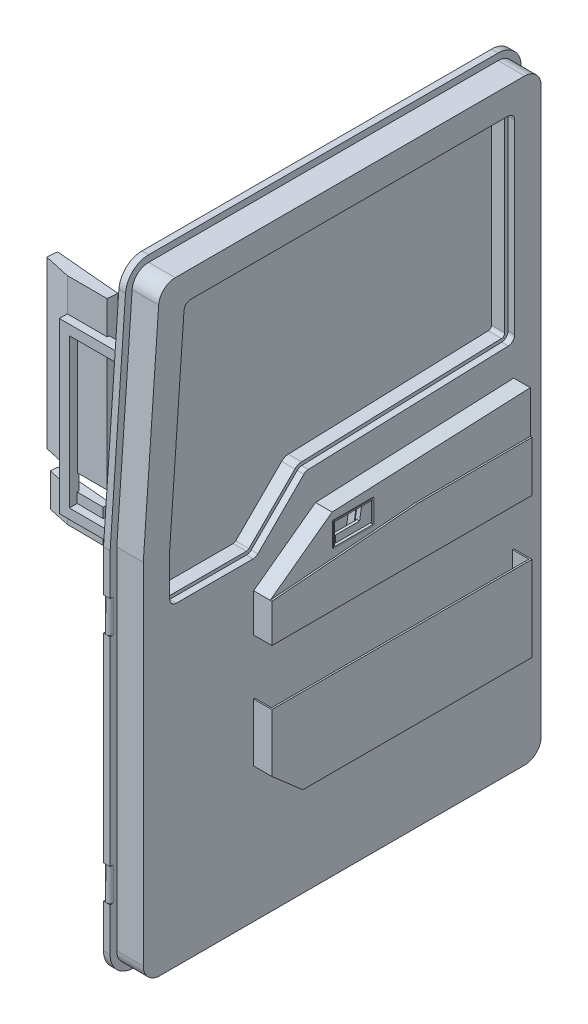
SolidWorks part; units mm, degrees
ref_plane "Front Plane" through (0, 0, 0) normal (0, 0, 1) x (1, 0, 0)
ref_plane "Top Plane" through (0, 0, 0) normal (0, 1, 0) x (1, 0, 0)
ref_plane "Right Plane" through (0, 0, 0) normal (1, 0, 0) x (0, 0, -1)
ref_plane "Plane1" through (950, 0, 0) normal (1, 0, 0) x (0, 0, -1)
sketch "Sketch1" plane through (950, 0, 0) normal (1, 0, 0) x (0, 0, -1)
  line L0 (-750, -200) -> (-750, 1110) construction
  line L1 (-550, 0) -> (550, 0)
  line L2 (-600, 50) -> (-600, 1104.6439)
  line L3 (-503.7259, 1800) -> (550, 1800)
  line L4 (600, 50) -> (600, 1750)
  line L5 (-750, 1110) -> (-699.9479, 1809.9761) construction
  line L6 (-699.9479, 1809.9761) -> (-739.9479, 1809.9761) construction
  line L7 (-739.9479, 1809.9761) -> (-739.9479, 1909.9761) construction
  line L8 (-750, -200) -> (600, -200) construction
  line L9 (600, -200) -> (600, 0) construction
  line L10 (-600, 1104.6439) -> (-553.5985, 1753.5662)
  line L11 (-503.7259, 1820) -> (550, 1820)
  line L12 (620, 50) -> (620, 1750)
  line L13 (-550, -20) -> (550, -20)
  line L14 (-620, 50) -> (-620, 1105.3581)
  line L15 (-620, 1105.3581) -> (-573.5476, 1754.9926)
  arc A0 (-553.5985, 1753.5662) -> (-503.7259, 1800) centre (-503.7259, 1750) cw
  arc A1 (550, 1800) -> (600, 1750) centre (550, 1750) cw
  arc A2 (550, 0) -> (600, 50) centre (550, 50) ccw
  arc A3 (-550, 0) -> (-600, 50) centre (-550, 50) cw
  arc A4 (550, 1820) -> (620, 1750) centre (550, 1750) cw
  arc A5 (550, -20) -> (620, 50) centre (550, 50) ccw
  arc A6 (-550, -20) -> (-620, 50) centre (-550, 50) cw
  arc A7 (-573.5476, 1754.9926) -> (-503.7259, 1820) centre (-503.7259, 1750) cw
  point P16 (600, 1800)
  point P22 (-600, 0)
  dimension "D11" = 50
  dimension "D1" = 1200
  dimension "D2" = 1800
  dimension "D3" = 200
  dimension "D4" = 100
  dimension "D5" = 40
  dimension "D6" = 2110
  dimension "D7" = 150
  dimension "D8" = 1310
  dimension "D9" = 175.91
  dimension "D10" = 150
  dimension "D12" = 20
extrude "Boss-Extrude1" add sketch "Sketch1" against normal blind 20
extrude "Boss-Extrude2" add sketch "Sketch1<2>" against normal blind 100 contours A3 L1 A2 L4 A1 L3 A0 L10 L2 region at (950, 894.6381, -4.6785)
sketch "Sketch1<2>" plane through (950, 0, 0) normal (1, 0, 0) x (0, 0, -1) same geometry as "Sketch1"
sketch "Sketch2" plane through (950, 0, 0) normal (1, 0, 0) x (0, 0, -1)
  line L9 (-520.2547, 1098.2257) -> (-520.2547, 968.2257)
  line L10 (-500.2547, 948.2257) -> (-268.6753, 948.2257)
  line L11 (-254.5499, 954.0669) -> (-115.6202, 1092.6683)
  line L12 (520, 50) -> (520, 1720)
  line L13 (520, 1720) -> (-475.7944, 1720)
  line L14 (-475.7944, 1720) -> (-520.2547, 1098.2257)
  line L15 (520, 1139.3207) -> (520, 1700)
  line L16 (500, 1720) -> (-457.1735, 1720)
  line L17 (-477.1225, 1701.4265) -> (-520.2547, 1098.2257)
  line L18 (-102.1855, 1098.4975) -> (500.6908, 1119.3327)
  line L19 (500, 1710) -> (-457.1735, 1710)
  line L20 (-467.148, 1700.7132) -> (-510.2547, 1097.8687)
  line L21 (-510.2547, 1097.8687) -> (-510.2547, 968.2257)
  line L22 (-500.2547, 958.2257) -> (-268.6753, 958.2257)
  line L23 (-261.6126, 961.1463) -> (-122.6829, 1099.7477)
  line L24 (-102.5309, 1108.4915) -> (500.3454, 1129.3267)
  line L25 (510, 1139.3207) -> (510, 1700)
  arc A6 (520, 1700) -> (500, 1720) centre (500, 1700) ccw
  arc A7 (500.6908, 1119.3327) -> (520, 1139.3207) centre (500, 1139.3207) ccw
  arc A8 (-115.6202, 1092.6683) -> (-102.1855, 1098.4975) centre (-101.4948, 1078.5094) cw
  arc A9 (-268.6753, 948.2257) -> (-254.5499, 954.0669) centre (-268.6753, 968.2257) ccw
  arc A10 (-457.1735, 1720) -> (-477.1225, 1701.4265) centre (-457.1735, 1700) ccw
  arc A11 (-520.2547, 968.2257) -> (-500.2547, 948.2257) centre (-500.2547, 968.2257) ccw
  arc A12 (-457.1735, 1710) -> (-467.148, 1700.7132) centre (-457.1735, 1700) ccw
  arc A13 (-510.2547, 968.2257) -> (-500.2547, 958.2257) centre (-500.2547, 968.2257) ccw
  arc A14 (-268.6753, 958.2257) -> (-261.6126, 961.1463) centre (-268.6753, 968.2257) ccw
  arc A15 (-122.6829, 1099.7477) -> (-102.5309, 1108.4915) centre (-101.4948, 1078.5094) cw
  arc A16 (500.3454, 1129.3267) -> (510, 1139.3207) centre (500, 1139.3207) ccw
  arc A17 (510, 1700) -> (500, 1710) centre (500, 1700) ccw
  point P13 (520, 1120)
  point P16 (-110.0496, 1098.2257)
  point P19 (-260.4048, 948.2257)
  point P25 (-520.2547, 948.2257)
  dimension "D6" = 20
  dimension "D2" = 600
  dimension "D3" = 621.7743
  dimension "D4" = 150
  dimension "D5" = 150
  dimension "D1" = 100
  dimension "D7" = 10
extrude "Cut-Extrude1" cut sketch "Sketch2" against normal blind 20
extrude "Cut-Extrude2" cut sketch "Sketch2<2>" against normal blind 30 contours L25 A17 L19 A12 L20 L21 A13 L22 A14 L23 A15 L24 A16 region at (950, 1382.3885, 18.9303)
sketch "Sketch2<2>" plane through (950, 0, 0) normal (1, 0, 0) x (0, 0, -1) same geometry as "Sketch2"
sketch "Sketch3" plane through (850, 0, 0) normal (-1, 0, 0) x (0, 0, 1)
  line L0 (-520, 1700) -> (-520, 1139.3207)
  line L1 (-500, 1710) -> (457.1735, 1710)
  line L2 (-500.6908, 1119.3327) -> (102.1855, 1098.4975)
  line L3 (115.6202, 1092.6683) -> (254.5499, 954.0669)
  line L4 (268.6753, 948.2257) -> (500.2547, 948.2257)
  line L5 (520.2547, 968.2257) -> (520.2547, 1098.2257)
  line L6 (520.2547, 1098.2257) -> (477.1225, 1701.4265)
  line L7 (-500, 1720) -> (457.1735, 1720)
  line L8 (510.2547, 1097.8687) -> (467.148, 1700.7132)
  line L9 (510.2547, 968.2257) -> (510.2547, 1097.8687)
  line L10 (268.6753, 958.2257) -> (500.2547, 958.2257)
  line L11 (122.6829, 1099.7477) -> (261.6126, 961.1463)
  line L12 (-500.3454, 1129.3267) -> (102.5309, 1108.4915)
  line L13 (-510, 1700) -> (-510, 1139.3207)
  arc A0 (-520, 1139.3207) -> (-500.6908, 1119.3327) centre (-500, 1139.3207) ccw
  arc A1 (102.1855, 1098.4975) -> (115.6202, 1092.6683) centre (101.4948, 1078.5094) cw
  arc A2 (254.5499, 954.0669) -> (268.6753, 948.2257) centre (268.6753, 968.2257) ccw
  arc A5 (254.5499, 954.0669) -> (268.6753, 948.2257) centre (268.6753, 968.2257) ccw construction
  arc A6 (500.2547, 948.2257) -> (520.2547, 968.2257) centre (500.2547, 968.2257) ccw
  arc A7 (457.1735, 1720) -> (477.1225, 1701.4265) centre (457.1735, 1700) cw
  arc A8 (-520, 1700) -> (-500, 1720) centre (-500, 1700) cw
  arc A9 (-510, 1700) -> (-500, 1710) centre (-500, 1700) cw
  arc A10 (457.1735, 1710) -> (467.148, 1700.7132) centre (457.1735, 1700) cw
  arc A11 (500.2547, 958.2257) -> (510.2547, 968.2257) centre (500.2547, 968.2257) ccw
  arc A12 (261.6126, 961.1463) -> (268.6753, 958.2257) centre (268.6753, 968.2257) ccw
  arc A13 (102.5309, 1108.4915) -> (122.6829, 1099.7477) centre (101.4948, 1078.5094) cw
  arc A14 (-510, 1139.3207) -> (-500.3454, 1129.3267) centre (-500, 1139.3207) ccw
  dimension "D1" = 10
extrude "Cut-Extrude3" cut sketch "Sketch3" against normal blind 20
extrude "Cut-Extrude4" cut sketch "Sketch3<2>" against normal blind 60 contours L13 A14 L12 A13 L11 A12 L10 A11 L9 L8 A10 L1 A9 region at (850, 1382.3885, 18.9303)
sketch "Sketch3<2>" plane through (850, 0, 0) normal (-1, 0, 0) x (0, 0, 1) same geometry as "Sketch3"
ref_plane "Plane2" through (0, 180, 0) normal (0, -1, 0) x (1, 0, 0)
sketch "Sketch4" plane through (0, 180, 0) normal (0, -1, 0) x (1, 0, 0)
  line L0 (930, 573.5476) -> (930, 620) construction
  line L2 (930, 620) -> (950, 620) construction
  line L3 (930, 610) -> (930, 624.5561)
  line L4 (930, 624.5561) -> (950, 624.5561)
  line L5 (950, 624.5561) -> (950, 610)
  circle A0 centre (940, 610) radius 10
  dimension "D1" = 20
extrude "Cut-Extrude5" cut sketch "Sketch4" against normal blind 100 contours A0 L5 L4 L3 region at (940, 180, 620.8334)
pattern_linear "LPattern1" count 2 spacing 700 along (0, 1, 0) of "Cut-Extrude5"
sketch "Sketch5" plane through (950, 0, 0) normal (1, 0, 0) x (0, 0, -1)
  line L0 (620, 50) -> (620, 1750) construction
  line L1 (460, 130) -> (300, 130)
  line L2 (470, 140) -> (470, 240)
  line L3 (460, 250) -> (300, 250)
  line L4 (290, 140) -> (290, 240)
  line L5 (-550, -20) -> (550, -20) construction
  line L6 (460, 253) -> (300, 253)
  line L7 (287, 140) -> (287, 240)
  line L8 (460, 127) -> (300, 127)
  line L9 (473, 140) -> (473, 240)
  arc A0 (470, 240) -> (460, 250) centre (460, 240) ccw
  arc A1 (460, 130) -> (470, 140) centre (460, 140) ccw
  arc A2 (300, 130) -> (290, 140) centre (300, 140) cw
  arc A3 (300, 250) -> (290, 240) centre (300, 240) ccw
  arc A4 (300, 253) -> (287, 240) centre (300, 240) ccw
  arc A5 (300, 127) -> (287, 140) centre (300, 140) cw
  arc A6 (460, 127) -> (473, 140) centre (460, 140) ccw
  arc A7 (473, 240) -> (460, 253) centre (460, 240) ccw
  point P10 (470, 250)
  point P13 (470, 130)
  point P16 (290, 130)
  dimension "D5" = 10
  dimension "D1" = 120
  dimension "D2" = 150
  dimension "D3" = 150
  dimension "D4" = 180
  dimension "D6" = 3
extrude "Cut-Extrude6" cut sketch "Sketch5" against normal blind 10 contours L3 A3 L4 A2 L1 A1 L2 A0 region at (950, 190, -380)
extrude "Boss-Extrude3" add sketch "Sketch5<3>" along normal blind 3
sketch "Sketch5<3>" plane through (950, 0, 0) normal (1, 0, 0) x (0, 0, -1) same geometry as "Sketch5"
sketch "Sketch6" plane through (940, 0, 0) normal (1, 0, 0) x (0, 0, -1)
  line L0 (300, 130) -> (460, 130) construction
  line L1 (305, 240) -> (445, 240)
  line L2 (300, 235) -> (300, 145)
  line L3 (305, 140) -> (445, 140)
  line L4 (450, 235) -> (450, 145)
  line L5 (290, 240) -> (290, 140) construction
  arc A0 (300, 145) -> (305, 140) centre (305, 145) ccw
  arc A1 (445, 140) -> (450, 145) centre (445, 145) ccw
  arc A2 (445, 240) -> (450, 235) centre (445, 235) cw
  arc A3 (305, 240) -> (300, 235) centre (305, 235) ccw
  point P10 (300, 140)
  point P15 (450, 240)
  point P18 (300, 240)
  dimension "D5" = 5
  dimension "D1" = 150
  dimension "D2" = 100
  dimension "D3" = 10
  dimension "D4" = 10
extrude "Boss-Extrude4" add sketch "Sketch6" along normal blind 10
sketch "Sketch10" plane through (950, 0, 0) normal (1, 0, 0) x (0, 0, -1)
  line L0 (324.7973, 190) -> (300, 190) construction
  line L1 (325.7973, 195) -> (323.7973, 195)
  line L2 (325.7973, 195) -> (325.7973, 185)
  line L3 (325.7973, 185) -> (323.7973, 185)
  line L4 (323.7973, 195) -> (323.7973, 185)
  line L5 (325.7973, 195) -> (323.7973, 185) construction
  line L6 (325.7973, 185) -> (323.7973, 195) construction
  line L7 (300, 235) -> (300, 145) construction
  circle A0 centre (324.7973, 190) radius 15
  dimension "D1" = 30
  dimension "D2" = 2
  dimension "D3" = 10
extrude "Boss-Extrude5" add sketch "Sketch10" along normal blind 1
extrude "Cut-Extrude8" cut sketch "Sketch10<2>" against normal blind 20 contours L1 L4 L3 L2 region at (950, 190, -324.7973)
sketch "Sketch10<2>" plane through (950, 0, 0) normal (1, 0, 0) x (0, 0, -1) same geometry as "Sketch10"
sketch "Sketch11" plane through (951, 0, 0) normal (1, 0, 0) x (0, 0, -1)
  circle A0 centre (324.7973, 190) radius 10.3287
extrude "Cut-Extrude-Thin1" cut sketch "Sketch11" against normal blind 5 thin thin type one direction wall 1
sketch "Sketch12" plane through (950, 0, 0) normal (1, 0, 0) x (0, 0, -1)
  line L0 (-477.1225, 1701.4265) -> (-520.2547, 1098.2257) construction
  line L1 (-523.1149, 1058.2257) -> (-553.1149, 1058.2257)
  line L2 (-523.1149, 1058.2257) -> (-523.1149, 1088.2257)
  line L3 (-523.1149, 1088.2257) -> (-553.1149, 1088.2257)
  line L4 (-553.1149, 1058.2257) -> (-553.1149, 1088.2257)
  line L5 (-500.2547, 958.2257) -> (-268.6753, 958.2257) construction
  line L6 (-523.1149, 1568.2257) -> (-553.1149, 1568.2257)
  line L7 (-523.1149, 1568.2257) -> (-523.1149, 1538.2257)
  line L8 (-523.1149, 1538.2257) -> (-553.1149, 1538.2257)
  line L9 (-553.1149, 1568.2257) -> (-553.1149, 1538.2257)
  dimension "D1" = 30
  dimension "D2" = 30
  dimension "D3" = 30
  dimension "D4" = 30
  dimension "D5" = 450
  dimension "D6" = 100
extrude "Boss-Extrude6" add sketch "Sketch12" along normal blind 200
sketch "Sketch13" plane through (1150, 0, 0) normal (1, 0, 0) x (0, 0, -1)
  line L0 (-553.1149, 1058.2257) -> (-523.1149, 1058.2257) construction
  line L1 (-553.1149, 1568.2257) -> (-523.1149, 1568.2257)
  line L2 (-553.1149, 1568.2257) -> (-553.1149, 1058.2257)
  line L3 (-553.1149, 1058.2257) -> (-523.1149, 1058.2257)
  line L4 (-523.1149, 1568.2257) -> (-523.1149, 1058.2257)
  line L5 (-523.1149, 1058.2257) -> (-523.1149, 1088.2257) construction
extrude "Boss-Extrude7" add sketch "Sketch13" against normal blind 30
ref_plane "Plane3" through (0, 1668.2257, 0) normal (0, 1, 0) x (-1, 0, 0)
sketch "Sketch14" plane through (0, 1668.2257, 0) normal (0, 1, 0) x (-1, 0, 0)
  line L0 (-1030, 529.1365) -> (-1229.2389, 511.7053) construction
  line L1 (-1030, 529.1365) -> (-1027.3853, 499.2506)
  line L2 (-1229.2389, 511.7053) -> (-1226.6243, 481.8195)
  line L3 (-1027.3853, 499.2506) -> (-1226.6243, 481.8195)
  line L4 (-1030, 529.1365) -> (-1150, 529.1365)
  line L5 (-1150, 523.1149) -> (-1150, 553.1149) construction
  line L6 (-950, 573.5476) -> (-950, 503.7259) construction
  line L7 (-1150, 529.1365) -> (-1229.2389, 511.7053)
  dimension "D1" = 5
  dimension "D2" = 200
  dimension "D3" = 80
  dimension "D4" = 30
extrude "Boss-Extrude8" add sketch "Sketch14" against normal blind 500
sketch "Sketch15" plane through (51.1511, 0, 584.66) normal (-0.0872, 0, -0.9962) x (-0.9962, 0, 0.0872)
  line L12 (-983.9633, 1664.2257) -> (-1175.9633, 1664.2257)
  line L13 (-1175.9633, 1664.2257) -> (-1175.9633, 1172.2257)
  line L14 (-1175.9633, 1172.2257) -> (-983.9633, 1172.2257)
  line L15 (-983.9633, 1172.2257) -> (-983.9633, 1664.2257)
  line L16 (-983.9633, 1664.2257) -> (-1175.9633, 1664.2257)
  line L17 (-1175.9633, 1664.2257) -> (-1175.9633, 1172.2257)
  line L18 (-1175.9633, 1172.2257) -> (-983.9633, 1172.2257)
  line L19 (-983.9633, 1172.2257) -> (-983.9633, 1664.2257)
  dimension "D1" = 4
extrude "Cut-Extrude9" cut sketch "Sketch15" against normal blind 10
sketch "Sketch16" plane through (52.0227, 0, 594.622) normal (-0.0872, 0, -0.9962) x (-0.9962, 0, 0.0872)
  line L0 (-1175.9633, 1172.2257) -> (-983.9633, 1172.2257) construction
  line L1 (-983.9633, 1172.2257) -> (-983.9633, 1664.2257) construction
  circle A0 centre (-1053.9633, 1242.2257) radius 50
  dimension "D3" = 100
  dimension "D1" = 70
  dimension "D2" = 70
extrude "Boss-Extrude9" add sketch "Sketch16" along normal blind 0.5
dome "Dome1" faces to dome 1 distance 5 reverse direction no elliptical dome no face at (1052.122, 1242.2257, 506.6227) parameters "D1"=5
ref_plane "Plane4" through (0, 1118.2257, 0) normal (0, -1, 0) x (1, 0, 0)
sketch "Sketch18" plane through (0, 1118.2257, 0) normal (0, -1, 0) x (1, 0, 0)
  line L0 (1039.3644, 508.2408) -> (1213.6985, 492.9885)
  line L1 (1039.3644, 508.2408) -> (1041.2644, 529.9582)
  line L2 (1213.6985, 492.9885) -> (1215.5985, 514.706)
  line L3 (1041.2644, 529.9582) -> (1215.5985, 514.706) construction
  line L5 (1226.6243, 481.8195) -> (1027.3853, 499.2506) construction
  line L6 (1215.5985, 514.706) -> (1150, 529.1365)
  line L7 (1150, 553.1149) -> (1150, 523.1149) construction
  line L8 (1150, 529.1365) -> (1229.2389, 511.7053) construction
  line L9 (1150, 529.1365) -> (1041.2644, 529.9582)
  dimension "D1" = 10
  dimension "D2" = 175
extrude "Boss-Extrude10" add sketch "Sketch18" along normal blind 100
sketch "Sketch19" plane through (850, 0, 0) normal (-1, 0, 0) x (0, 0, 1)
  line L0 (-517.1737, 1027.2796) -> (80.5914, 1001.2898)
  line L1 (80.5914, 1001.2898) -> (267.2454, 864.2527)
  line L2 (267.2454, 864.2527) -> (267.2454, 748.48)
  line L3 (267.2454, 748.48) -> (-517.1737, 748.48)
  line L4 (-517.1737, 748.48) -> (-517.1737, 1027.2796)
  line L5 (267.2454, 581.3838) -> (267.2454, 406.5274)
  line L6 (267.2454, 406.5274) -> (173.9184, 325.1988)
  line L7 (173.9184, 325.1988) -> (-517.1737, 325.1988)
  line L8 (-517.1737, 325.1988) -> (-517.1737, 581.3838)
  line L9 (263.2454, 581.3838) -> (263.2454, 408.3473)
  line L10 (263.2454, 408.3473) -> (172.4201, 329.1988)
  line L11 (172.4201, 329.1988) -> (-513.1737, 329.1988)
  line L12 (-513.1737, 329.1988) -> (-513.1737, 581.3838)
  line L13 (-517.1737, 581.3838) -> (-513.1737, 581.3838)
  line L14 (267.2454, 581.3838) -> (263.2454, 581.3838)
  dimension "D1" = 4
extrude "Boss-Extrude11" add sketch "Sketch19" along normal blind 50
sketch "Sketch20" plane through (800, 0, 0) normal (-1, 0, 0) x (0, 0, 1)
  line L0 (-517.1737, 581.3838) -> (267.2454, 581.3838)
  line L1 (267.2454, 581.3838) -> (267.2454, 406.5274)
  line L2 (267.2454, 406.5274) -> (173.9184, 325.1988)
  line L3 (173.9184, 325.1988) -> (-517.1737, 325.1988)
  line L4 (-517.1737, 325.1988) -> (-517.1737, 581.3838)
  line L5 (-517.1737, 900) -> (-517.1737, 748.48)
  line L6 (-517.1737, 748.48) -> (267.2454, 748.48)
  line L7 (267.2454, 748.48) -> (267.2454, 864.2527)
  line L8 (267.2454, 864.2527) -> (-171.6276, 900)
  line L9 (-171.6276, 900) -> (-517.1737, 900)
extrude "Boss-Extrude12" add sketch "Sketch20" along normal blind 5
sketch "Sketch21" plane through (800, 0, 0) normal (-1, 0, 0) x (0, 0, 1)
  line L1 (74.7593, 974.3228) -> (-40.7347, 974.3228)
  line L2 (74.7593, 974.3228) -> (74.7593, 909.2873)
  line L3 (74.7593, 909.2873) -> (-40.7347, 909.2873)
  line L4 (-40.7347, 974.3228) -> (-40.7347, 909.2873)
extrude "Cut-Extrude10" cut sketch "Sketch21" against normal blind 15
sketch "Sketch22" plane through (815, 0, 0) normal (-1, 0, 0) x (0, 0, 1)
  line L0 (-40.7347, 974.3228) -> (-40.7347, 909.2873) construction
  line L1 (-40.7347, 971.0503) -> (-10.489, 971.0503)
  line L2 (-40.7347, 971.0503) -> (-40.7347, 913.1895)
  line L3 (-40.7347, 913.1895) -> (-4.3054, 913.1895)
  line L4 (-4.3054, 934.3904) -> (-4.3054, 913.1895)
  line L5 (-10.489, 971.0503) -> (-4.3054, 934.3904)
extrude "Boss-Extrude13" add sketch "Sketch22" along normal blind 5
sketch "Sketch23" plane through (810, 0, 0) normal (-1, 0, 0) x (0, 0, 1)
  line L0 (-40.7347, 971.0503) -> (-10.489, 971.0503)
  line L1 (-10.489, 971.0503) -> (-4.3054, 934.3904)
  line L2 (-4.3054, 934.3904) -> (68.5727, 934.3904)
  line L3 (68.5727, 934.3904) -> (68.5727, 913.1895)
  line L4 (68.5727, 913.1895) -> (-40.7347, 913.1895)
  line L5 (-40.7347, 913.1895) -> (-40.7347, 971.0503)
extrude "Boss-Extrude14" add sketch "Sketch23" along normal blind 8
sketch "Sketch24" plane through (800, 0, 0) normal (-1, 0, 0) x (0, 0, 1)
  line L0 (-44.7347, 976.3228) -> (-44.7347, 907.2873)
  line L1 (-40.7347, 974.3228) -> (74.7593, 974.3228)
  line L2 (-40.7347, 974.3228) -> (-40.7347, 909.2873)
  line L3 (-40.7347, 909.2873) -> (74.7593, 909.2873)
  line L4 (74.7593, 974.3228) -> (74.7593, 909.2873)
  line L5 (-42.7347, 905.2873) -> (76.7593, 905.2873)
  line L6 (78.7593, 976.3228) -> (78.7593, 907.2873)
  line L7 (-42.7347, 978.3228) -> (76.7593, 978.3228)
  line L8 (-44.7347, 978.3228) -> (-44.7347, 905.2873) construction
  line L9 (-44.7347, 905.2873) -> (78.7593, 905.2873) construction
  line L10 (78.7593, 978.3228) -> (78.7593, 905.2873) construction
  line L11 (-44.7347, 978.3228) -> (78.7593, 978.3228) construction
  arc A0 (-44.7347, 907.2873) -> (-42.7347, 905.2873) centre (-42.7347, 907.2873) ccw
  arc A1 (76.7593, 905.2873) -> (78.7593, 907.2873) centre (76.7593, 907.2873) ccw
  arc A2 (78.7593, 976.3228) -> (76.7593, 978.3228) centre (76.7593, 976.3228) ccw
  arc A3 (-44.7347, 976.3228) -> (-42.7347, 978.3228) centre (-42.7347, 976.3228) cw
  dimension "D2" = 2
  dimension "D1" = 4
extrude "Boss-Extrude15" add sketch "Sketch24" along normal blind 2
sketch "Sketch25" plane through (815, 0, 0) normal (-1, 0, 0) x (0, 0, 1)
  line L0 (-9.0127, 974.3228) -> (1.9571, 909.2873)
  line L1 (74.7593, 974.3228) -> (-40.7347, 974.3228) construction
  line L2 (-40.7347, 909.2873) -> (74.7593, 909.2873) construction
  line L3 (1.9571, 909.2873) -> (74.7593, 909.2873)
  line L4 (74.7593, 909.2873) -> (74.7593, 974.3228)
  line L5 (74.7593, 909.2873) -> (74.7593, 974.3228) construction
  line L6 (74.7593, 909.2873) -> (74.7593, 974.3228) construction
  line L7 (74.7593, 974.3228) -> (-9.0127, 974.3228)
  line L8 (-4.3054, 934.3904) -> (-10.489, 971.0503) construction
  line L9 (-4.3054, 934.3904) -> (-10.489, 971.0503) construction
  dimension "D1" = 2
extrude "Cut-Extrude11" cut sketch "Sketch25" against normal blind 20
sketch "Sketch26" plane through (0, 0, 0) normal (0, -1, 0) x (1, 0, 0)
  line L0 (930, 550) -> (930, -550) construction
  line L1 (930, 217.5704) -> (-930, 217.5704)
  line L2 (930, 217.5704) -> (930, -69.4083)
  line L3 (930, -69.4083) -> (-930, -69.4083)
  line L4 (-930, 217.5704) -> (-930, -69.4083)
  dimension "D1" = 1860
extrude "Boss-Extrude16" add sketch "Sketch26" along normal blind 10
mirror "Mirror2" about plane through (0, 0, 0) normal (1, 0, 0) of "Cut-Extrude4", "Cut-Extrude3", "Cut-Extrude2", "Cut-Extrude1", "Boss-Extrude2", "Boss-Extrude1"
mirror "Mirror3" about plane through (0, 0, 0) normal (1, 0, 0) of "Boss-Extrude7", "Boss-Extrude6", "Cut-Extrude-Thin1", "Cut-Extrude8", "Boss-Extrude5", "Boss-Extrude4", "Boss-Extrude3", "Cut-Extrude6", "LPattern1", "Cut-Extrude5"
mirror "Mirror5" about plane through (0, 0, 0) normal (1, 0, 0) of "Dome1", "Boss-Extrude9", "Cut-Extrude9", "Boss-Extrude8"
mirror "Mirror6" about plane through (0, 0, 0) normal (1, 0, 0) of "Boss-Extrude16", "Cut-Extrude11", "Boss-Extrude15", "Boss-Extrude14", "Boss-Extrude13", "Cut-Extrude10", "Boss-Extrude12", "Boss-Extrude11", "Boss-Extrude10"
sketch "Sketch27" plane through (0, -10, 0) normal (0, -1, 0) x (1, 0, 0)
  line L0 (-930, 550) -> (-930, 217.5704) construction
  line L1 (-930, 274.7898) -> (930, 274.7898)
  line L2 (-930, 274.7898) -> (-930, -98.6265)
  line L3 (-930, -98.6265) -> (930, -98.6265)
  line L4 (930, 274.7898) -> (930, -98.6265)
  line L5 (930, -69.4083) -> (930, -550) construction
extrude "Cut-Extrude12" cut sketch "Sketch27" against normal blind 10
sketch "Sketch28" plane through (0, -20, 0) normal (0, -1, 0) x (1, 0, 0)
  line L1 (416.4484, 823.7811) -> (1825.4672, 823.7811)
  line L2 (416.4484, 823.7811) -> (416.4484, -1008.9287)
  line L3 (416.4484, -1008.9287) -> (1825.4672, -1008.9287)
  line L4 (1825.4672, 823.7811) -> (1825.4672, -1008.9287)
extrude "Cut-Extrude13" cut sketch "Sketch28" against normal through all
